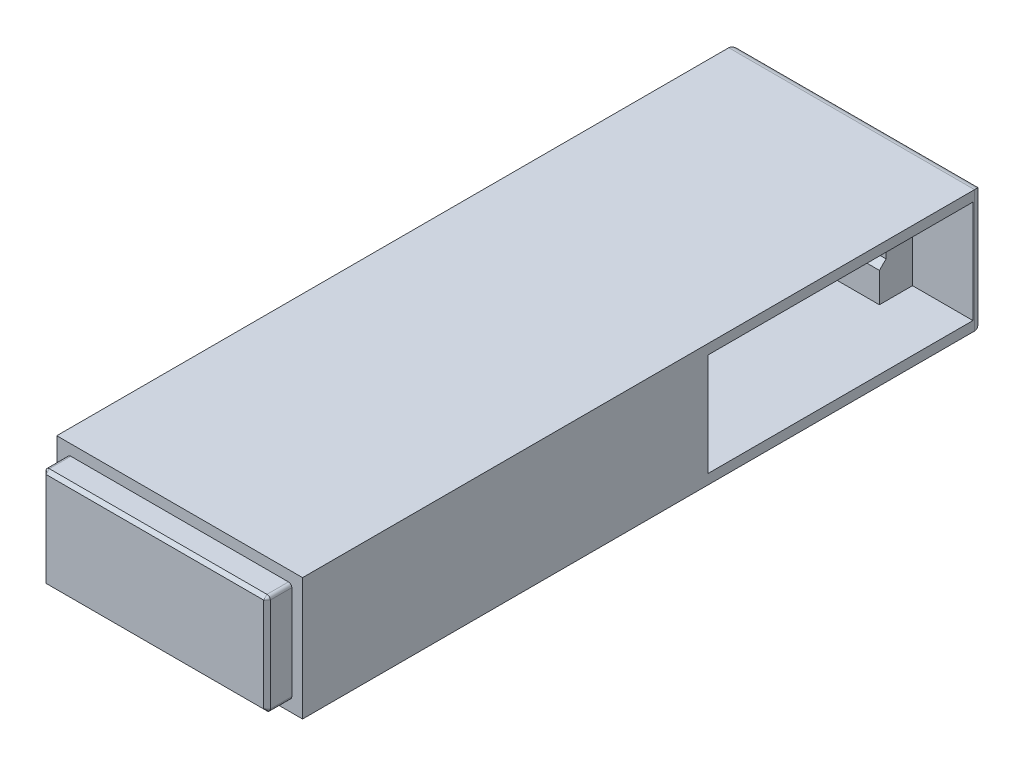
SolidWorks part; units mm, degrees
material "PLA"
ref_plane "Ön Düzlem" through (0, 0, 0) normal (0, 0, 1) x (1, 0, 0)
ref_plane "Üst Düzlem" through (0, 0, 0) normal (0, 1, 0) x (1, 0, 0)
ref_plane "Sağ Düzlem" through (0, 0, 0) normal (1, 0, 0) x (0, 0, -1)
sketch "Çizim1" plane through (0, 0, 0) normal (0, 0, 1) x (1, 0, 0)
  line L1 (-14.85, -7.4) -> (14.85, -7.4)
  line L2 (-14.85, -7.4) -> (-14.85, 7.4)
  line L3 (-14.85, 7.4) -> (14.85, 7.4)
  line L4 (14.85, -7.4) -> (14.85, 7.4)
  line L5 (-14.85, -7.4) -> (14.85, 7.4) construction
  line L6 (-14.85, 7.4) -> (14.85, -7.4) construction
  point P0 (0, 0)
  dimension "D1" = 29.7
  dimension "D2" = 14.8
extrude "Yükseklik-Ekstrüzyon1" add sketch "Çizim1" along normal blind 82.2
sketch "Çizim2" plane through (14.85, 0, 0) normal (1, 0, 0) x (0, 0, -1)
  line L0 (0, -7.4) -> (0, 7.4) construction
  line L1 (-33.2, 6.2) -> (-1.2, 6.2)
  line L2 (-33.2, 6.2) -> (-33.2, -6.2)
  line L3 (-33.2, -6.2) -> (-1.2, -6.2)
  line L4 (-1.2, 6.2) -> (-1.2, -6.2)
  line L5 (-82.2, 7.4) -> (0, 7.4) construction
  line L6 (-82.2, -7.4) -> (0, -7.4) construction
  dimension "D1" = 1.2
  dimension "D2" = 32
  dimension "D3" = 1.2
  dimension "D4" = 1.2
extrude "Kes-Ekstrüzyon1" cut sketch "Çizim2" against normal blind 25
sketch "Çizim3" plane through (14.85, 0, 0) normal (1, 0, 0) x (0, 0, -1)
  line L0 (-17.2, 6.2) -> (-17.2, -6.2) construction
  line L1 (-1.2, 6.2) -> (-33.2, 6.2) construction
  line L2 (-33.2, -6.2) -> (-1.2, -6.2) construction
  line L3 (-33.2, 6.2) -> (-33.2, -6.2)
  line L4 (-33.2, -6.2) -> (-1.2, -6.2) construction
  line L5 (-33.2, 6.2) -> (-33.2, -6.2) construction
  line L6 (-33.2, -6.2) -> (-29.2, -6.2)
  line L7 (-29.2, -6.2) -> (-29.2, 6.2)
  line L8 (-1.2, 6.2) -> (-33.2, 6.2) construction
  line L9 (-29.2, 6.2) -> (-33.2, 6.2)
  line L10 (-31.45, 6.2) -> (-31.45, -6.2) construction
  line L11 (-1.2, -6.2) -> (-5.2, -6.2)
  line L12 (-5.2, -6.2) -> (-5.2, 6.2)
  line L13 (-5.2, 6.2) -> (-1.2, 6.2)
  line L14 (-1.2, 6.2) -> (-1.2, -6.2)
  circle A0 centre (-31.45, 0) radius 0.85
  circle A1 centre (-2.95, 0) radius 0.85
  dimension "D1" = 1.7
  dimension "D2" = 12
  dimension "D3" = 14.25
extrude "Yükseklik-Ekstrüzyon2" add sketch "Çizim3" against normal blind 7 from offset 7.3 offset against normal yes
sketch "Çizim4" plane through (0.55, 0, 0) normal (-1, 0, 0) x (0, 0, 1)
  circle A0 centre (31.45, 0) radius 0.85
  circle A1 centre (31.45, 0) radius 0.85
  circle A2 centre (2.95, 0) radius 0.85
  circle A3 centre (2.95, 0) radius 0.85
extrude "Yükseklik-Ekstrüzyon3" add sketch "Çizim4" against normal blind 0.2
chamfer "Pah1" distance 6.2 angle 30 4 edges at (0.55, -6.2, 3.2) (0.55, 6.2, 3.2) (0.55, -6.2, 31.2) (0.55, 6.2, 31.2) first distance on face at (0.55, 0, 3.2) first distance on face at (0.55, 0, 31.2)
sketch "Çizim5" plane through (0, -6.2, 0) normal (0, 1, 0) x (1, 0, 0)
  line L0 (-10.15, -33.2) -> (-10.15, -1.2) construction
  line L1 (-1.95, -5.2) -> (-10.15, -5.2)
  line L2 (-1.95, -5.2) -> (-1.95, -1.2)
  line L3 (-1.95, -1.2) -> (-10.15, -1.2)
  line L4 (-10.15, -5.2) -> (-10.15, -1.2)
  line L5 (7.55, -1.2) -> (14.85, -1.2) construction
  dimension "D1" = 8.2
  dimension "D2" = 4
extrude "Kes-Ekstrüzyon2" cut sketch "Çizim5" against normal through all and the other way blind 3.2
sketch "Çizim6" plane through (0, 0, 0) normal (0, 0, 1) x (1, 0, 0)
  line L0 (15.45, -6) -> (15.45, 15)
  line L1 (0, 0) -> (0, 15) construction
  line L2 (-15.45, 15) -> (15.45, 15)
  line L3 (-15.45, 15) -> (-15.45, -6)
  line L4 (15.45, -6) -> (19.45, -6)
  line L5 (19.45, -6) -> (19.45, 19)
  line L6 (14.85, -7.4) -> (14.85, 7.4) construction
  line L7 (-15.45, -6) -> (-19.45, -6)
  line L8 (-19.45, -6) -> (-19.45, 19)
  line L9 (-19.45, 19) -> (19.45, 19)
  line L10 (19.45, 0) -> (-19.45, 0) construction
  point P8 (0, 15)
  dimension "D1" = 4.6
  dimension "D2" = 4
  dimension "D3" = 4
  dimension "D4" = 6
  dimension "D5" = 15
fillet "Radyus1" radius 1 4 edges at (0, -7.4, 0) (0, 7.4, 0) (-14.85, 0, 0) (14.85, 0, 0)
sketch "Çizim7" plane through (-10.15, 0, 0) normal (1, 0, 0) x (0, 0, -1)
  line L0 (-33.2, 0) -> (-1, 0) construction
  line L1 (-33.2, 6.2) -> (-33.2, -6.2) construction
  line L2 (-1, -7.4) -> (-1, 7.4) construction
  circle A0 centre (-11, 0) radius 1.4
  dimension "D1" = 11
  dimension "D2" = 2.8
extrude "Kes-Ekstrüzyon3" cut sketch "Çizim7" against normal through all
sketch "Çizim8" plane through (0, 0, 82.2) normal (0, 0, 1) x (1, 0, 0)
  line L1 (-13.55, -6.1) -> (13.55, -6.1)
  line L2 (-13.55, -6.1) -> (-13.55, 6.1)
  line L3 (-13.55, 6.1) -> (13.55, 6.1)
  line L4 (13.55, -6.1) -> (13.55, 6.1)
  line L5 (-13.55, -6.1) -> (13.55, 6.1) construction
  line L6 (-13.55, 6.1) -> (13.55, -6.1) construction
  line L7 (14.85, -7.4) -> (14.85, 7.4) construction
  point P0 (0, 0)
  dimension "D1" = 1.3
  dimension "D2" = 12.2
extrude "Yükseklik-Ekstrüzyon4" add sketch "Çizim8" along normal blind 3
fillet "Radyus2" radius 0.4 4 edges at (13.55, -6.1, 83.7) (-13.55, -6.1, 83.7) (13.55, 6.1, 83.7) (-13.55, 6.1, 83.7)
sketch "Çizim9" plane through (0, -7.4, 0) normal (0, -1, 0) x (1, 0, 0)
  line L0 (0, 0) -> (0, 82.2) construction
  line L1 (-14.85, 82.2) -> (14.85, 82.2) construction
  line L3 (2.5, 38) -> (4, 38)
  line L4 (2.5, 38) -> (2.5, 42)
  line L5 (2.5, 42) -> (4, 42)
  line L6 (4, 38) -> (4, 42)
  line L7 (2.5, 38) -> (4, 42) construction
  line L8 (2.5, 42) -> (4, 38) construction
  point P5 (3.25, 40)
  dimension "D1" = 1.5
  dimension "D2" = 4
  dimension "D3" = 40
  dimension "D4" = 2.5
revolve "Kes-Döndür1" cut sketch "Çizim9" angle 360 about L0
pattern_linear "LÇoğaltma1" count 2 spacing 35 along (0, 0, 1) of "Kes-Döndür1"
fillet "Radyus3" radius 0.5 8 edges at (-4, -7.4, 40) (4, -7.4, 40) (-4, -7.4, 75) (4, -7.4, 75) (2.5, -7.4, 75) (-2.5, -7.4, 75) (-2.5, -7.4, 40) (2.5, -7.4, 40)
sketch "Çizim10" plane through (7.55, 0, 0) normal (1, 0, 0) x (0, 0, -1)
  line L0 (-5.2, 0) -> (0, 0) construction
  line L1 (-5.2, 6.2) -> (-5.2, -6.2) construction
  line L3 (-5.2, 1.6) -> (-4.4, 1.6)
  line L4 (-5.2, 1.6) -> (-5.2, -1.6)
  line L5 (-5.2, -1.6) -> (-4.4, -1.6)
  line L6 (-4.4, 1.6) -> (-4.4, -1.6)
  point P9 (-4.4, 0)
  dimension "D1" = 3.2
  dimension "D2" = 0.8
extrude "Kes-Ekstrüzyon4" cut sketch "Çizim10" against normal up to next
chamfer "Pah3" distance 1 angle 45 2 edges at (3.5881, -1.6, 5.2) (3.5881, 1.6, 5.2)
chamfer "Pah4" distance 0.4 angle 45 8 edges at (-13.4328, -5.9828, 85.2) (-13.55, 0, 85.2) (-13.4328, 5.9828, 85.2) (0, 6.1, 85.2) (13.4328, 5.9828, 85.2) (13.55, 0, 85.2) (13.4328, -5.9828, 85.2) (0, -6.1, 85.2)
sketch "Çizim12" plane through (-10.15, 0, 0) normal (1, 0, 0) x (0, 0, -1)
  line L1 (-7.7668, 0) -> (-9.3834, 2.8)
  line L2 (-9.3834, 2.8) -> (-12.6166, 2.8)
  line L3 (-12.6166, 2.8) -> (-14.2332, 0)
  line L4 (-14.2332, 0) -> (-12.6166, -2.8)
  line L5 (-12.6166, -2.8) -> (-9.3834, -2.8)
  line L6 (-9.3834, -2.8) -> (-7.7668, 0)
  circle A0 centre (-11, 0) radius 2.8 construction
  dimension "D1" = 5.6
extrude "Kes-Ekstrüzyon5" cut sketch "Çizim12" against normal blind 3.7
